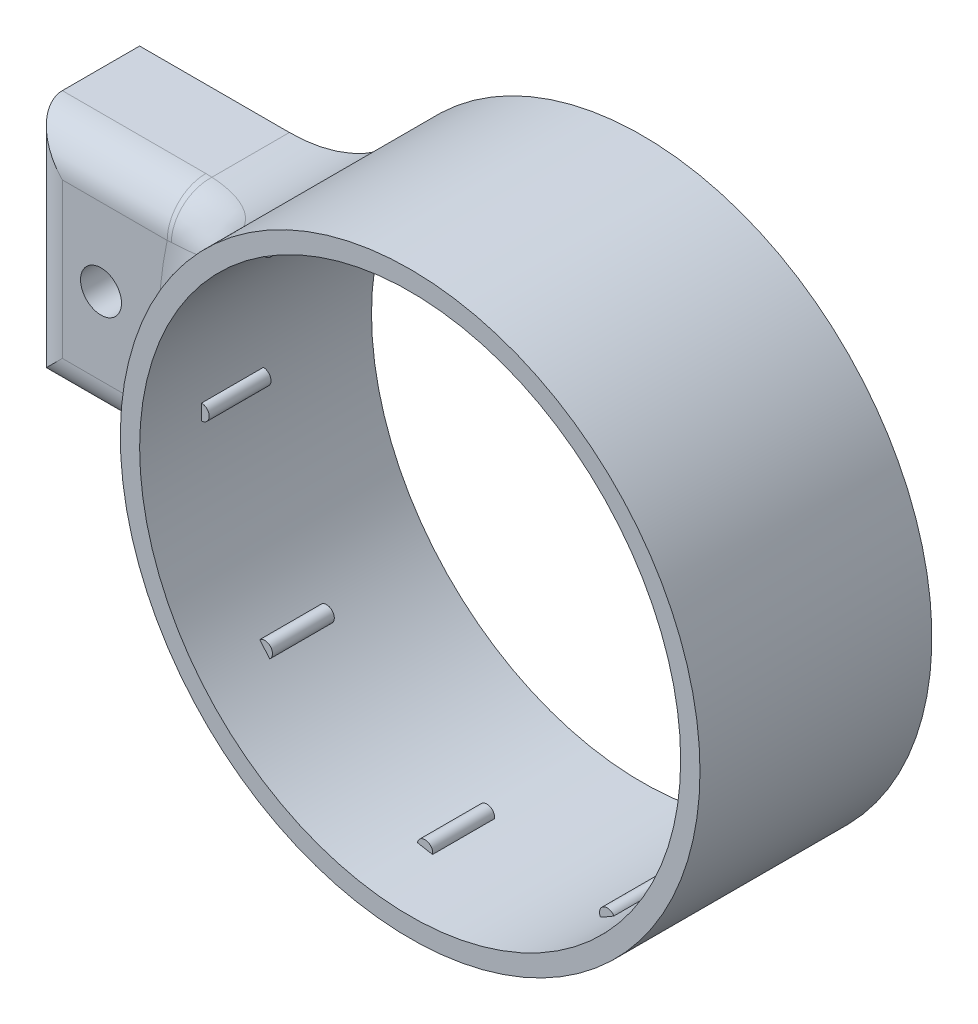
SolidWorks part; units mm, degrees
ref_plane "Plan de face" through (0, 0, 0) normal (0, 0, 1) x (1, 0, 0)
ref_plane "Plan de dessus" through (0, 0, 0) normal (0, 1, 0) x (1, 0, 0)
ref_plane "Plan de droite" through (0, 0, 0) normal (1, 0, 0) x (0, 0, -1)
sketch "Esquisse5" plane through (0, 0, 0) normal (0, 0, 1) x (1, 0, 0)
  line L0 (-1000, 0) -> (49000, 0) construction
  line L1 (-45.6207, 15) -> (-65, 15)
  line L2 (-65, 15) -> (-65, -15)
  line L3 (-45.6207, -15) -> (-65, -15)
  circle A0 centre (0, 0) radius 35
  arc A1 (-29.7526, -22.8261) -> (-29.7526, 22.8261) centre (0, 0) ccw
  arc A2 (-45.6207, 15) -> (-29.7526, 22.8261) centre (-45.6207, 35) ccw
  arc A3 (-45.6207, -15) -> (-29.7526, -22.8261) centre (-45.6207, -35) cw
  point P14 (-65, 0)
  dimension "D1" = 70
  dimension "D2" = 75
  dimension "D5" = 20
  dimension "D3" = 15
  dimension "D4" = 65
extrude "Boss.-Extru.4" add sketch "Esquisse5" along normal blind 15
sketch "Esquisse8" plane through (0, 0, 15) normal (0, 0, 1) x (1, 0, 0)
  circle A0 centre (0, 0) radius 35
  circle A1 centre (0, 0) radius 37.5
  circle A2 centre (0, 0) radius 35 construction
  arc A3 (-29.7526, -22.8261) -> (-29.7526, 22.8261) centre (0, 0) ccw construction
extrude "Boss.-Extru.7" add sketch "Esquisse8" along normal blind 15
ref_plane "Plan1" through (0, 0, 14) normal (0, 0, 1) x (1, 0, 0)
sketch "Esquisse15" plane through (0, 0, 14) normal (0, 0, 1) x (1, 0, 0)
  circle A39 centre (-35, 0) radius 1
  circle A40 centre (0, 0) radius 35 construction
  dimension "D1" = 2
extrude "Boss.-Extru.8" add sketch "Esquisse15" along normal blind 8
pattern_circular "Répétition circulaire1" count 9 over 360 about axis through (0, 0, 30) along (0, 0, 1) of "Boss.-Extru.8"
fillet "Congé3" radius 10 1 edges at (-37.5, 0, 15)
fillet "Congé4" radius 5 7 edges at (-45.3438, 15.0019, 15) (-45.3438, -15.0019, 15) (-36.9031, 16.9999, 17.733) (-55.3104, 15, 15) (-65, 0, 15) (-55.3104, -15, 15) (-36.9031, -16.9999, 17.733)
sketch "Esquisse12" plane through (-65, 0, 0) normal (-1, 0, 0) x (0, 0, 1)
  line L5 (0, 10) -> (10, 10) construction
  line L8 (0, 15) -> (0, -15) construction
  line L9 (10, 10) -> (10, -10) construction
  line L10 (-1000, 0) -> (49000, 0) construction
  line L11 (0, -10) -> (10, -10) construction
  line L12 (10, 15) -> (0, 15) construction
  line L14 (0, 10) -> (0, -10) construction
  line L15 (-0.2, 10.2) -> (10.2, 10.2)
  line L16 (10.2, 10.2) -> (10.2, -10.2)
  line L17 (-0.2, -10.2) -> (10.2, -10.2)
  line L18 (-0.2, 10.2) -> (-0.2, -10.2)
  line L20 (15, -10) -> (15, 10) construction
  point P9 (10, 0)
  dimension "D1" = 5
  dimension "D2" = 5
  dimension "D3" = 0.2
extrude "Enlèv. mat.-Extru.2" cut sketch "Esquisse12" against normal blind 25
sketch "Esquisse13" plane through (0, 0, 15) normal (0, 0, 1) x (1, 0, 0)
  line L0 (-64.996, -10.2) -> (-64.996, 10.2) construction
  circle A0 centre (-54.996, 0) radius 2.65
  dimension "D1" = 5.3
  dimension "D2" = 10
extrude "Enlèv. mat.-Extru.3" cut sketch "Esquisse13" against normal up to next and the other way through all
